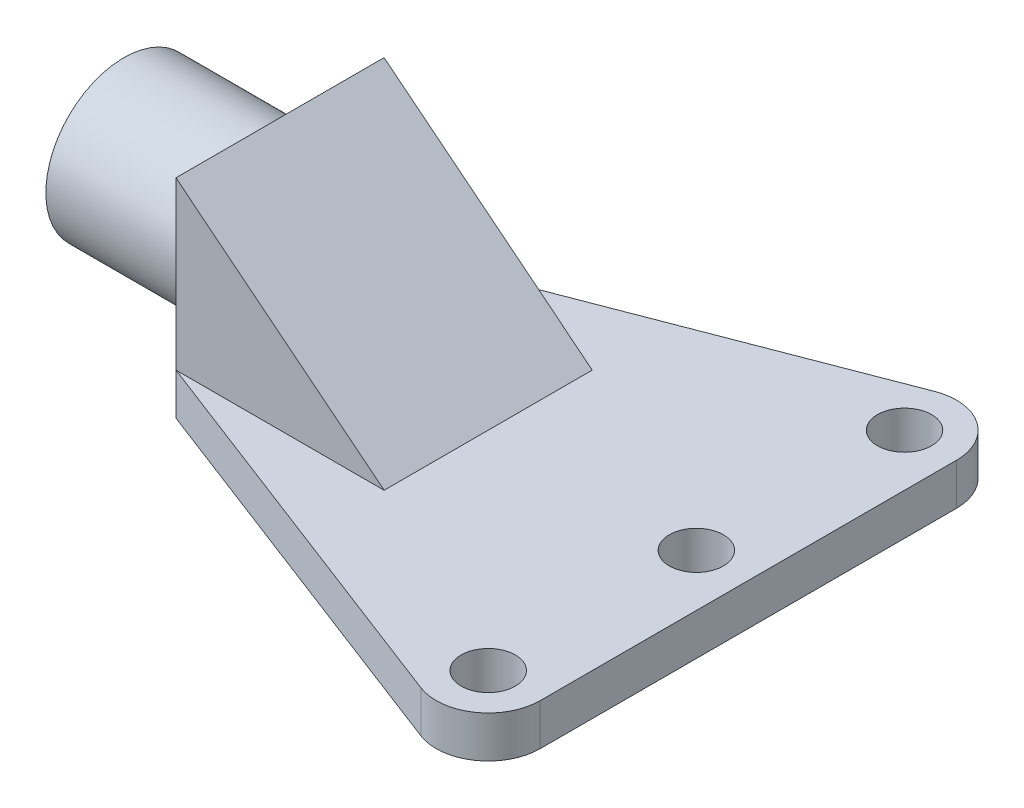
SolidWorks part; units mm, degrees
ref_plane "Front Plane" through (0, 0, 0) normal (0, 0, 1) x (1, 0, 0)
ref_plane "Top Plane" through (0, 0, 0) normal (0, 1, 0) x (1, 0, 0)
ref_plane "Right Plane" through (0, 0, 0) normal (1, 0, 0) x (0, 0, -1)
sketch "Sketch1" plane through (0, 0, 0) normal (0, 1, 0) x (1, 0, 0)
  line L0 (0, 0) -> (0, 25.4)
  line L1 (0, 0) -> (0, -25.4)
  line L2 (0, 0) -> (-38.1, 0)
  line L3 (-50.8, -12.7) -> (-2.2757, -31.3279)
  line L4 (-50.8, -12.7) -> (-25.4, -12.7)
  line L5 (-50.8, -12.7) -> (-50.8, 12.7)
  line L6 (-50.8, 12.7) -> (-25.4, 12.7)
  line L7 (-25.4, -12.7) -> (-25.4, 12.7)
  line L8 (-50.8, -12.7) -> (-25.4, 12.7) construction
  line L9 (-50.8, 12.7) -> (-25.4, -12.7) construction
  line L10 (-50.8, 12.7) -> (-2.2758, 31.3282)
  line L11 (0, 25.4) -> (6.35, 25.4)
  line L12 (6.35, 25.4) -> (6.3497, -25.4)
  circle A0 centre (0, 25.4) radius 3.302
  circle A1 centre (0, -25.4) radius 3.302
  arc A2 (-2.2757, -31.3279) -> (6.3497, -25.4) centre (0, -25.4) ccw
  arc A3 (6.35, 25.4) -> (-2.2758, 31.3282) centre (0, 25.4) ccw
sketch "Sketch2" plane through (0, 0, 0) normal (0, 1, 0) x (1, 0, 0)
  line L0 (-50.8, -12.7) -> (-25.4, -12.7)
  line L1 (-50.8, -12.7) -> (-50.8, 12.7)
  line L2 (-50.8, 12.7) -> (-25.4, 12.7)
  line L3 (-25.4, -12.7) -> (-25.4, 12.7)
extrude "Boss-Extrude1" add sketch "Sketch2" along normal blind 25.4
sketch "Sketch4" plane through (0, 0, 0) normal (0, 1, 0) x (1, 0, 0)
  line L0 (-50.8, -12.7) -> (-2.2757, -31.3279)
  line L1 (-50.8, -12.7) -> (-50.8, 12.7)
  line L2 (-50.8, 12.7) -> (-2.2758, 31.3282)
  line L3 (6.35, 25.4) -> (6.3497, -25.4)
  arc A0 (-2.2757, -31.3279) -> (6.3497, -25.4) centre (0, -25.4) ccw
  arc A1 (6.35, 25.4) -> (-2.2758, 31.3282) centre (0, 25.4) ccw
extrude "Boss-Extrude2" add sketch "Sketch4" along normal blind 5.08 separate body
sketch "Sketch5" plane through (0, 0, 0) normal (0, 1, 0) x (1, 0, 0)
  circle A0 centre (0, -25.4) radius 3.302
extrude "Cut-Extrude1" cut sketch "Sketch5" along normal up to next (5.08 mm away)
sketch "Sketch6" plane through (0, 0, 0) normal (0, 1, 0) x (1, 0, 0)
  circle A0 centre (0, 25.4) radius 3.302
extrude "Cut-Extrude2" cut sketch "Sketch6" along normal up to next (5.08 mm away)
sketch "Sketch7" plane through (0, 0, -12.7) normal (0, 0, -1) x (-1, 0, 0)
  line L0 (50.8, 25.4) -> (25.4, 5.08)
  line L1 (25.4, 25.4) -> (25.4, 0) construction
  line L2 (50.8, 5.08) -> (2.2757, 5.08) construction
  line L3 (25.4, 5.08) -> (25.4, 25.4)
  line L4 (25.4, 25.4) -> (50.8, 25.4)
sketch "Sketch8" plane through (0, 0, -12.7) normal (0, 0, -1) x (-1, 0, 0)
  line L0 (50.8, 25.4) -> (25.4, 5.08)
  line L1 (25.4, 5.08) -> (25.4, 25.4)
  line L2 (25.4, 25.4) -> (50.8, 25.4)
extrude "Cut-Extrude3" cut sketch "Sketch8" against normal up to next (25.4 mm away)
sketch "Sketch9" plane through (-50.8, 0, 0) normal (-1, 0, 0) x (0, 0, 1)
  line L0 (0, 25.4) -> (0, 0)
  line L1 (-12.7, 25.4) -> (12.7, 25.4) construction
  circle A0 centre (0, 12.7) radius 9.525
sketch "Sketch10" plane through (-50.8, 0, 0) normal (-1, 0, 0) x (0, 0, 1)
  circle A0 centre (0, 12.7) radius 9.525
extrude "Boss-Extrude3" add sketch "Sketch10" along normal blind 19.05
sketch "Sketch11" plane through (0, 0, 0) normal (0, 1, 0) x (1, 0, 0)
  circle A0 centre (0, 0) radius 3.302
sketch "Sketch12" plane through (0, 0, 0) normal (0, 1, 0) x (1, 0, 0)
  circle A0 centre (0, 0) radius 3.302
extrude "Cut-Extrude4" cut sketch "Sketch12" along normal up to next
